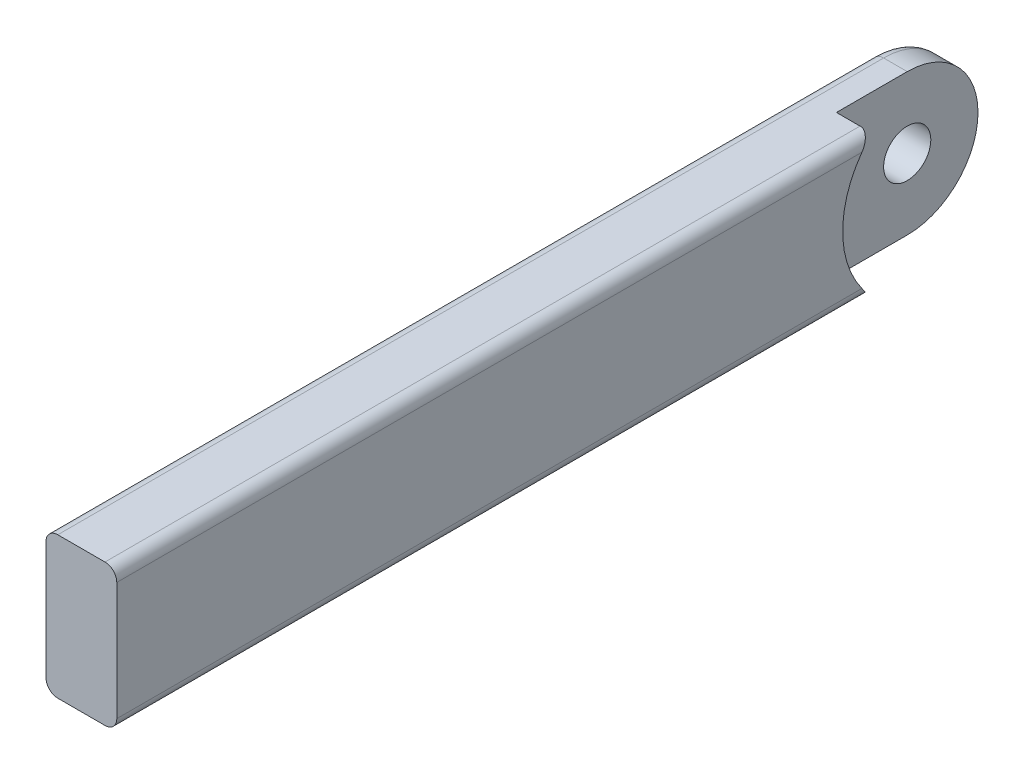
SolidWorks part; units mm, degrees
ref_plane "Front Plane" through (0, 0, 0) normal (0, 0, 1) x (1, 0, 0)
ref_plane "Top Plane" through (0, 0, 0) normal (0, 1, 0) x (1, 0, 0)
ref_plane "Right Plane" through (0, 0, 0) normal (1, 0, 0) x (0, 0, -1)
sketch "Sketch1" plane through (0, 0, 0) normal (0, 1, 0) x (1, 0, 0)
  line L1 (-26.4527, 29.8986) -> (-11.4527, 29.8986)
  line L2 (-26.4527, 29.8986) -> (-26.4527, -160.1014)
  line L3 (-26.4527, -160.1014) -> (-11.4527, -160.1014)
  line L4 (-11.4527, 29.8986) -> (-11.4527, -160.1014)
  line L5 (-26.4527, 29.8986) -> (-11.4527, -160.1014) construction
  line L6 (-26.4527, -160.1014) -> (-11.4527, 29.8986) construction
  dimension "D1" = 15
  dimension "D2" = 190
extrude "Boss-Extrude1" add sketch "Sketch1" along normal blind 30
sketch "Sketch2" plane through (0, 0, -29.8986) normal (0, 0, -1) x (-1, 0, 0)
  line L0 (11.4527, 0) -> (26.4527, 0) construction
  line L1 (11.4527, 30) -> (18.9527, 30)
  line L2 (11.4527, 30) -> (11.4527, 0)
  line L3 (11.4527, 0) -> (18.9527, 0)
  line L4 (18.9527, 30) -> (18.9527, 0)
extrude "Cut-Extrude1" cut sketch "Sketch2" against normal blind 30
sketch "Sketch4" plane through (-18.9527, 0, 0) normal (1, 0, 0) x (0, 0, -1)
  line L0 (-0.1014, 0) -> (29.8986, 30)
  line L1 (29.8986, 30) -> (29.8986, 0)
  line L2 (29.8986, 0) -> (-0.1014, 30)
  circle A0 centre (14.8986, 15) radius 5
  dimension "D1" = 10
extrude "Cut-Extrude2" cut sketch "Sketch4" against normal blind 30 contours A0
fillet "Fillet2" radius 15 2 edges at (-22.7027, 0, -29.8986) (-22.7027, 30, -29.8986)
sketch "Sketch5" plane through (-18.9527, 0, 0) normal (1, 0, 0) x (0, 0, -1)
  circle A0 centre (14.8986, 15) radius 21.1761
extrude "Cut-Extrude3" cut sketch "Sketch5" along normal blind 30
fillet "Fillet4" radius 2.5 6 edges at (-26.4527, 0, 72.6014) (-26.4527, 4.3934, -25.5053) (-26.4527, 25.6066, -25.5053) (-26.4527, 30, 72.6014) (-11.4527, 30, 80.1014) (-11.4527, 0, 80.1014)
